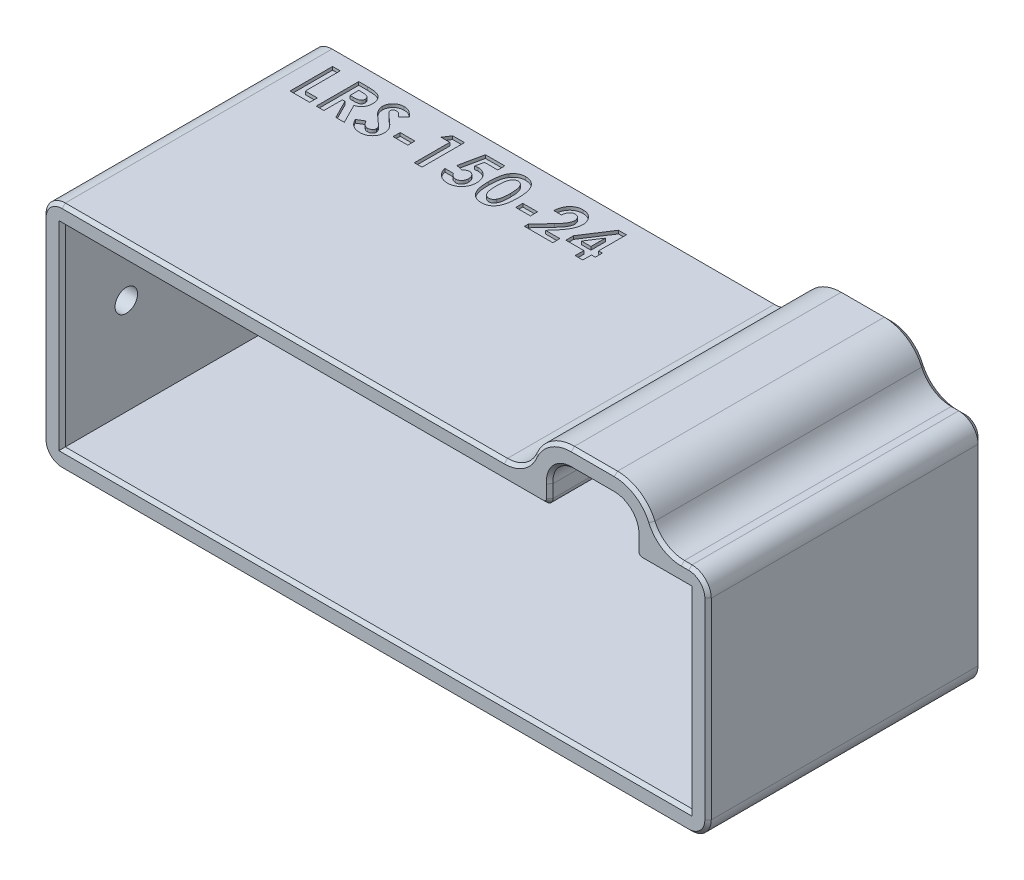
SolidWorks part; units mm, degrees
ref_plane "Front Plane" through (0, 0, 0) normal (0, 0, 1) x (1, 0, 0)
ref_plane "Top Plane" through (0, 0, 0) normal (0, 1, 0) x (1, 0, 0)
ref_plane "Right Plane" through (0, 0, 0) normal (1, 0, 0) x (0, 0, -1)
sketch "Sketch1" plane through (0, 0, 0) normal (0, 0, 1) x (1, 0, 0)
  line L0 (-51.75, -18) -> (-51.75, 18)
  line L1 (-48.75, -15) -> (48.75, -15)
  line L2 (-48.75, -15) -> (-48.75, 15)
  line L3 (-48.75, 15) -> (48.75, 15)
  line L4 (48.75, -15) -> (48.75, 15)
  line L5 (-48.75, -15) -> (48.75, 15) construction
  line L6 (-48.75, 15) -> (48.75, -15) construction
  line L7 (-51.75, 18) -> (51.75, 18)
  line L8 (51.75, -18) -> (51.75, 18)
  line L9 (-51.75, -18) -> (51.75, -18)
  point P0 (0, 0)
  dimension "D2" = 97.5
  dimension "D3" = 30
  dimension "D1" = 3
extrude "Boss-Extrude1" add sketch "Sketch1" along normal blind 40
extrude "Boss-Extrude2" add sketch "Sketch1<2>" against normal blind 3 contours L9 L8 L7 L0
sketch "Sketch1<2>" plane through (0, 0, 0) normal (0, 0, 1) x (1, 0, 0) same geometry as "Sketch1"
sketch "Sketch2" plane through (-51.75, 0, 0) normal (-1, 0, 0) x (0, 0, 1)
  line L0 (30, -18) -> (30, 0) construction
  line L1 (40, -18) -> (-3, -18) construction
  line L2 (30, 0) -> (30, 18) construction
  line L3 (40, 18) -> (-3, 18) construction
  line L4 (0, -15) -> (0, 15) construction
  circle A0 centre (30, 0) radius 1.75
  dimension "D1" = 3.5
  dimension "D2" = 30
extrude "Cut-Extrude1" cut sketch "Sketch2" against normal blind 3
sketch "Sketch3" plane through (0, 0, 40) normal (0, 0, 1) x (1, 0, 0)
  line L0 (-51.75, 18) -> (-51.75, 24.7)
  line L1 (-51.75, 24.7) -> (51.75, 24.7)
  line L2 (51.75, 24.7) -> (51.75, 18)
  line L3 (48.75, 15) -> (48.75, 21.7)
  line L4 (-48.75, 15) -> (-48.75, 21.7)
  line L5 (-48.75, 21.7) -> (48.75, 21.7)
  line L6 (30.47, 18.35) -> (37.17, 18.35) construction
  line L7 (30.47, 21.7) -> (37.17, 21.7)
  line L8 (30.47, 15) -> (37.17, 15)
  arc A0 (30.47, 21.7) -> (30.47, 15) centre (30.47, 18.35) ccw
  arc A1 (37.17, 15) -> (37.17, 21.7) centre (37.17, 18.35) ccw
  point P14 (33.82, 18.35)
  line M10 (51.75, 18) -> (-51.75, 18)
  dimension "D1" = 3.35
  dimension "D2" = 6.7
  dimension "D3" = 3
extrude "Boss-Extrude3" add sketch "Sketch3" against normal up to surface (43 mm away) contours L4 L5 L3 L2 L1 L0 M10 | A0 L5 L4 M10 | A1 L3 L5 M10 region at (0, 22.9765, 40) region at (-10.4857, 19.8594, 40) region at (44.2783, 19.9306, 40) up to face at (0, 0, -3)
sketch "Sketch4" plane through (0, 0, 40) normal (0, 0, 1) x (1, 0, 0)
  line L0 (48.75, 15) -> (-48.75, 15) construction
  line L5 (27.1384, 18) -> (40.5017, 18)
  line L6 (27.1384, 18) -> (27.1384, 15)
  line L7 (27.1384, 15) -> (40.5017, 15)
  line L8 (40.5017, 18) -> (40.5017, 15)
extrude "Cut-Extrude3" cut sketch "Sketch4" against normal up to surface (40 mm away) up to face at (0, 0, 0)
sketch "Sketch6" plane through (0, 0, 40) normal (0, 0, 1) x (1, 0, 0)
  line L16 (51.75, 17.8678) -> (-51.75, 17.8678)
  line L17 (51.75, -18) -> (51.75, 24.7) construction
  line L18 (-51.75, 24.7) -> (-51.75, -18) construction
  line L19 (43.5017, 15) -> (43.5017, 17.8678)
  line L20 (37.17, 24.7) -> (30.47, 24.7)
  line L21 (24.1384, 17.8678) -> (24.1384, 15)
  line L22 (43.5017, 15) -> (43.5017, 17.8678)
  line L23 (37.17, 24.7) -> (30.47, 24.7)
  line L24 (24.1384, 17.8678) -> (24.1384, 15)
  line L25 (-51.75, 17.8678) -> (-51.75, 24.7)
  line L26 (-51.75, 24.7) -> (51.75, 24.7)
  line L27 (51.75, 24.7) -> (51.75, 17.8678)
  arc A12 (43.5017, 17.8678) -> (37.17, 24.7) centre (37.17, 18.35) ccw
  arc A13 (30.47, 24.7) -> (24.1384, 17.8678) centre (30.47, 18.35) ccw
  arc A14 (43.5017, 17.8678) -> (37.17, 24.7) centre (37.17, 18.35) ccw
  arc A15 (30.47, 24.7) -> (24.1384, 17.8678) centre (30.47, 18.35) ccw
  line M21 (51.75, -18) -> (51.75, 24.7)
  line M22 (51.75, 24.7) -> (-51.75, 24.7)
  line M23 (-51.75, 24.7) -> (-51.75, -18)
  dimension "D1" = 3
extrude "Cut-Extrude4" cut sketch "Sketch6" against normal up to surface (43 mm away) contours A15 L16 M22 M23 | A14 L16 M21 M22 region at (46.8969, 21.5502, 40) region at (-13.1686, 21.3167, 40) up to face at (33.82, 20.2208, -3)
sketch "Sketch7" plane through (0, 0, -3) normal (0, 0, -1) x (-1, 0, 0)
  line L2 (-40.5017, 18) -> (-27.1384, 18)
  line L3 (-30.47, 21.7) -> (-37.17, 21.7)
  line L4 (-40.5017, 18) -> (-27.1384, 18)
  line L5 (-30.47, 21.7) -> (-37.17, 21.7)
  arc A2 (-27.1384, 18) -> (-30.47, 21.7) centre (-30.47, 18.35) ccw
  arc A3 (-37.17, 21.7) -> (-40.5017, 18) centre (-37.17, 18.35) ccw
  arc A4 (-27.1384, 18) -> (-30.47, 21.7) centre (-30.47, 18.35) ccw
  arc A5 (-37.17, 21.7) -> (-40.5017, 18) centre (-37.17, 18.35) ccw
  dimension "D1" = 0
extrude "Boss-Extrude4" add sketch "Sketch7" against normal up to surface (3 mm away) up to face at (16.91, 8.25, 0)
fillet "Fillet1" radius 5 2 edges at (43.5017, 17.8678, 18.5) (24.1384, 17.8678, 18.5)
fillet "Fillet2" radius 3 4 edges at (51.75, -18, 18.5) (-51.75, -18, 18.5) (-51.75, 17.8678, 18.5) (51.75, 17.8678, 18.5)
chamfer "Chamfer1" distance 1 angle 45 14 edges at (50.8713, 16.9891, -3) (48.1661, 17.8678, -3) (51.75, -0.0661, -3) (44.839, 18.6874, -3) (50.8713, -17.1213, -3) (40.6537, 23.6591, -3) (0, -18, -3) (33.82, 24.7, -3) (-50.8713, -17.1213, -3) (26.9863, 23.6591, -3) (-51.75, -0.0661, -3) (22.801, 18.6874, -3) (-50.8713, 16.9891, -3) (-14.346, 17.8678, -3)
sketch "Sketch8" plane through (0, 17.8678, 0) normal (0, 1, 0) x (1, 0, 0)
  text T0 "<b>LRS-150-24</b>" font "Century Gothic" height in points 25
extrude "Cut-Extrude5" cut sketch "Sketch8" against normal blind 0.5
fillet "Fillet3" radius 1 2 edges at (40.5017, 15, 20) (27.1384, 15, 20)
chamfer "Chamfer2" distance 0.5 angle 45 12 edges at (27.9805, 20.5917, 40) (33.82, 21.7, 40) (27.1384, 17, 40) (39.6595, 20.5917, 40) (40.5017, 17, 40) (45.1258, 15, 40) (48.75, 0, 40) (0, -15, 40) (-48.75, 0, 40) (-11.3058, 15, 40) (40.7946, 15.2929, 40) (26.8455, 15.2929, 40)
chamfer "Chamfer3" distance 0.5 angle 45 14 edges at (50.8713, 16.9891, 40) (48.1661, 17.8678, 40) (51.75, -0.0661, 40) (44.839, 18.6874, 40) (50.8713, -17.1213, 40) (40.6537, 23.6591, 40) (0, -18, 40) (33.82, 24.7, 40) (-50.8713, -17.1213, 40) (26.9863, 23.6591, 40) (-51.75, -0.0661, 40) (22.801, 18.6874, 40) (-50.8713, 16.9891, 40) (-14.346, 17.8678, 40)
